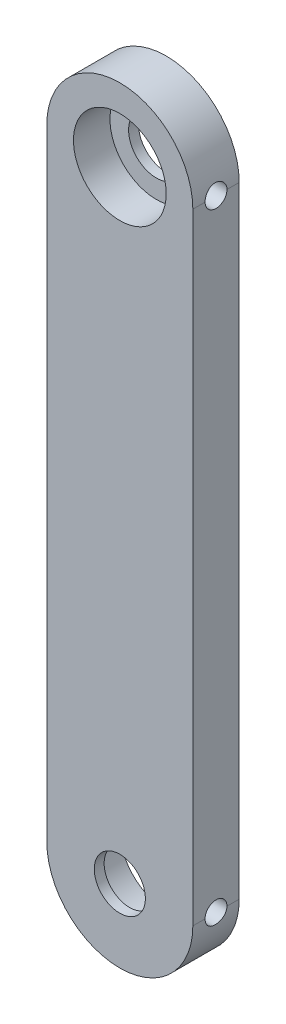
SolidWorks part; units mm, degrees
ref_plane "Alzado" through (0, 0, 0) normal (0, 0, 1) x (1, 0, 0)
ref_plane "Planta" through (0, 0, 0) normal (0, 1, 0) x (1, 0, 0)
ref_plane "Vista lateral" through (0, 0, 0) normal (1, 0, 0) x (0, 0, -1)
sketch "Croquis1" plane through (0, 0, 0) normal (0, 0, 1) x (1, 0, 0)
  line L0 (0, 42.5) -> (0, -42.5) construction
  line L1 (10, 42.5) -> (10, -42.5)
  line L2 (-10, 42.5) -> (-10, -42.5)
  arc A0 (10, 42.5) -> (-10, 42.5) centre (0, 42.5) ccw
  arc A1 (-10, -42.5) -> (10, -42.5) centre (0, -42.5) ccw
  point P2 (0, 0)
  point P8 (0, 52.5)
  point P9 (0, -52.5)
  dimension "D1" = 105
  dimension "D2" = 20
extrude "Saliente-Extruir1" add sketch "Croquis1" along normal blind 6.35
sketch "Croquis2" plane through (0, 0, 6.35) normal (0, 0, 1) x (1, 0, 0)
  circle A0 centre (0, 42.5) radius 6.35
  dimension "D1" = 12.7
extrude "Cortar-Extruir1" cut sketch "Croquis2" against normal blind 5
sketch "Croquis3" plane through (0, 0, 1.35) normal (0, 0, 1) x (1, 0, 0)
  circle A0 centre (0, 42.5) radius 3.8
  dimension "D1" = 7.6
extrude "Cortar-Extruir2" cut sketch "Croquis3" against normal through all
sketch "Croquis4" plane through (0, 0, 6.35) normal (0, 0, 1) x (1, 0, 0)
  line L0 (0, 42.5) -> (0, 30.5) construction
  line L1 (0, 30.5) -> (2, 30.5) construction
  circle A0 centre (5.175, 30.5) radius 3.175
  circle A1 centre (-5.175, 30.5) radius 3.175
  dimension "D3" = 6.35
  dimension "D1" = 2
  dimension "D2" = 12
extrude "Cortar-Extruir3" [suppressed] cut sketch "Croquis4" against normal blind 5
sketch "Croquis5" [suppressed] plane through (0, 0, 1.35) normal (0, 0, 1) x (1, 0, 0)
  circle A0 centre (-5.175, 30.5) radius 1.5
  circle A1 centre (5.175, 30.5) radius 1.5
  dimension "D1" = 3
  dimension "D2" = 3
extrude "Cortar-Extruir4" [suppressed] cut sketch "Croquis5" against normal blind 5
sketch "Croquis6" plane through (10, 0, 0) normal (1, 0, 0) x (0, 0, -1)
  line L0 (-6.35, 42.5) -> (0, 42.5) construction
  circle A0 centre (-3.175, 42.5) radius 1.5
  dimension "D1" = 3
extrude "Cortar-Extruir5" cut sketch "Croquis6" against normal blind 5
sketch "Croquis7" plane through (0, 0, 0) normal (0, 0, -1) x (-1, 0, 0)
  circle A0 centre (0, -42.5) radius 6.35
  dimension "D1" = 12.7
extrude "Cortar-Extruir6" cut sketch "Croquis7" against normal blind 5
sketch "Croquis8" plane through (0, 0, 5) normal (0, 0, -1) x (-1, 0, 0)
  circle A0 centre (0, -42.5) radius 3.5
  dimension "D1" = 7
extrude "Cortar-Extruir7" cut sketch "Croquis8" against normal blind 5
sketch "Croquis9" plane through (10, 0, 0) normal (1, 0, 0) x (0, 0, -1)
  line L0 (-6.35, -42.5) -> (0, -42.5) construction
  circle A0 centre (-3.175, -42.5) radius 1.5
  dimension "D1" = 3
extrude "Cortar-Extruir8" cut sketch "Croquis9" against normal blind 5
ref_axis "Eje1" through (0, 42.5, 1.35) along (0, 0, 1)
ref_axis "Eje2" through (0, -42.5, 5) along (0, 0, -1)
